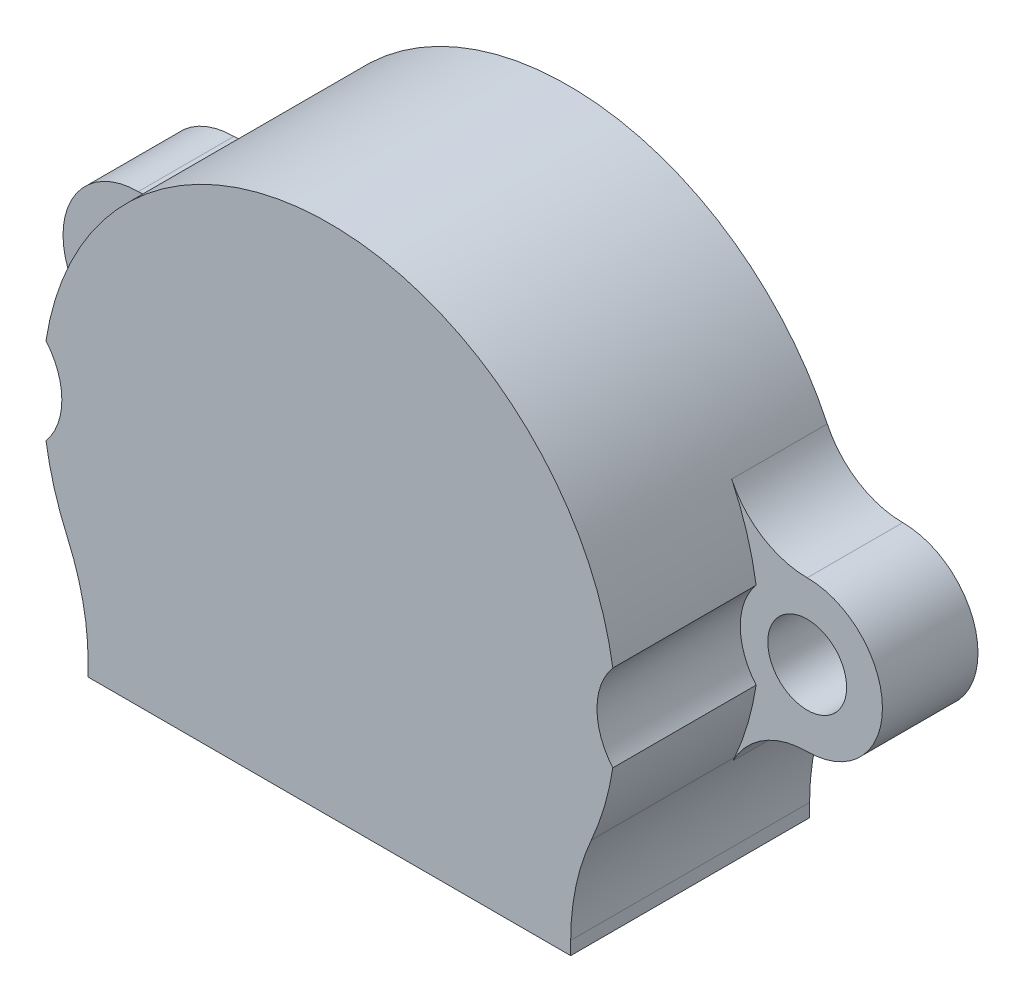
SolidWorks part; units mm, degrees
ref_plane "Front Plane" through (0, 0, 0) normal (0, 0, 1) x (1, 0, 0)
ref_plane "Top Plane" through (0, 0, 0) normal (0, 1, 0) x (1, 0, 0)
ref_plane "Right Plane" through (0, 0, 0) normal (1, 0, 0) x (0, 0, -1)
sketch "Sketch1" plane through (0, 0, 0) normal (0, 0, 1) x (1, 0, 0)
  line L0 (0, 0) -> (0, 12) construction
  line L1 (-7.6, -4.1307) -> (-7.6, -9.5)
  line L3 (7.6, -9.5) -> (7.6, -4.1307)
  line L4 (-7.6, -9.5) -> (-10.1, -9.5)
  line L5 (-10.1, -9.5) -> (-10.1, -6.48)
  line L6 (10.1, -6.48) -> (10.1, -9.5)
  line L7 (10.1, -9.5) -> (7.6, -9.5)
  arc A0 (7.6, -4.1307) -> (-7.6, -4.1307) centre (0, 0) ccw
  arc A1 (10.1, -6.48) -> (-10.1, -6.48) centre (0, 0) ccw
  point P1 (-7.4294, -4.4301)
  dimension "D1" = 17.3
  dimension "D2" = 24
  dimension "D3" = 15.2
  dimension "D4" = 2.5
  dimension "D5" = 9.5
extrude "Boss-Extrude1" add sketch "Sketch1" along normal blind 10
sketch "Sketch2" plane through (0, 0, 10) normal (0, 0, 1) x (1, 0, 0)
  line L0 (7.6, -4.1307) -> (7.6, -9.5) construction
  line L1 (-7.6, -9.5) -> (-7.6, -4.1307) construction
  line L2 (7.6, -4.1307) -> (7.6, -9.5)
  line L3 (-7.6, -9.5) -> (-7.6, -4.1307)
  line L4 (-7.6, -9.5) -> (7.6, -9.5)
  arc A0 (7.6, -4.1307) -> (-7.6, -4.1307) centre (0, 0) ccw construction
  arc A1 (7.6, -4.1307) -> (-7.6, -4.1307) centre (0, 0) ccw
extrude "Boss-Extrude2" add sketch "Sketch2" against normal blind 0.8
fillet "Fillet1" radius 10 2 edges at (-10.1, -6.48, 5) (10.1, -6.48, 5)
sketch "Sketch3" plane through (0, 0, 0) normal (0, 0, -1) x (-1, 0, 0)
  line L0 (0, 0) -> (14, 0) construction
  line L1 (0, 0) -> (0, 12) construction
  circle A0 centre (14, 0) radius 1.65
  arc A1 (10.9636, -4.8784) -> (-10.9636, -4.8784) centre (0, 0) ccw construction
  arc A2 (14, 3.15) -> (14, -3.15) centre (14, 0) cw
  arc A3 (14, -3.15) -> (10.8398, -5.1477) centre (14, -6.6484) ccw
  arc A5 (14, 3.15) -> (10.8398, 5.1477) centre (14, 6.6484) cw
  arc A14 (10.8398, 5.1477) -> (10.8398, -5.1477) centre (0, 0) cw
  arc A15 (-10.8398, 5.1477) -> (-10.8398, -5.1477) centre (0, 0) ccw
  arc A16 (-14, 3.15) -> (-10.8398, 5.1477) centre (-14, 6.6484) ccw
  arc A17 (-14, -3.15) -> (-10.8398, -5.1477) centre (-14, -6.6484) cw
  arc A18 (-14, 3.15) -> (-14, -3.15) centre (-14, 0) ccw
  circle A19 centre (-14, 0) radius 1.65
  point P21 (13.9223, 0)
  dimension "D1" = 3.3
  dimension "D2" = 1.5
  dimension "D3" = 14
extrude "Boss-Extrude4" add sketch "Sketch3" against normal blind 4
sketch "Sketch4" plane through (0, 0, 4) normal (0, 0, 1) x (1, 0, 0)
  circle A0 centre (-14, 0) radius 2.8
  circle A1 centre (14, 0) radius 2.8
  dimension "D1" = 5.6
extrude "Cut-Extrude1" cut sketch "Sketch4" along normal through all
